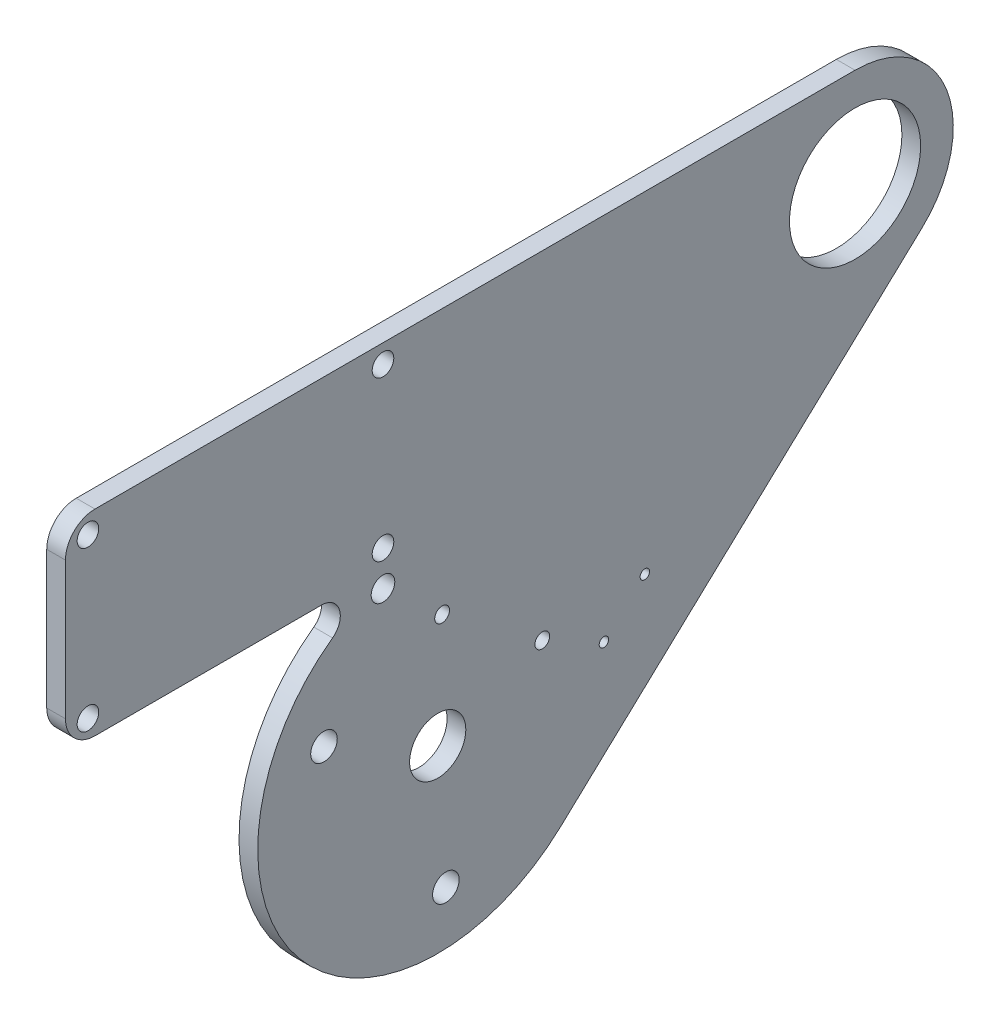
SolidWorks part; units mm, degrees
material "6061 Alloy"
ref_plane "Front Plane" through (0, 0, 0) normal (0, 0, 1) x (1, 0, 0)
ref_plane "Top Plane" through (0, 0, 0) normal (0, 1, 0) x (1, 0, 0)
ref_plane "Right Plane" through (0, 0, 0) normal (1, 0, 0) x (0, 0, -1)
sketch "Sketch1" plane through (0, 0, 0) normal (1, 0, 0) x (0, 0, -1)
  line L0 (-49.9001, -69.4268) -> (11.3662, -12.16)
  line L1 (-133.81, 16.645) -> (-76.19, 16.645)
  line L2 (-133.81, 16.645) -> (-133.81, -16.645)
  line L3 (-133.81, -16.645) -> (-76.19, -16.645)
  line L4 (-76.19, 16.645) -> (-76.19, -16.645)
  line L5 (-130, 13.475) -> (-80, 13.475)
  line L6 (-130, 13.475) -> (-130, -13.475)
  line L7 (-130, -13.475) -> (-80, -13.475)
  line L8 (-80, 13.475) -> (-80, -13.475)
  line L9 (-76.19, 16.645) -> (0, 16.645)
  line L10 (-83.2811, -19.3484) -> (-6.8511, 15.1697)
  line L11 (-130, -13.475) -> (-130, -19.435)
  line L12 (-80, -13.475) -> (-80, -19.435)
  line L13 (-76.19, -16.645) -> (0, -16.645)
  circle A0 centre (0, 0) radius 11.1125
  circle A1 centre (-70.7273, -47.145) radius 4.7625
  circle A2 centre (-70.7273, -47.145) radius 23.015 construction
  circle A3 centre (-70.7273, -47.145) radius 30.5
  circle A4 centre (0, 0) radius 16.645
  circle A5 centre (-130, -19.435) radius 2
  circle A6 centre (-80, -19.435) radius 2
  point P4 (-133.81, 0)
  point P12 (-130, 0)
  dimension "D6" = 22.225
  dimension "D7" = 9.525
  dimension "D8" = 46.03
  dimension "D9" = 61
  dimension "D11" = 0
  dimension "D14" = 4
  dimension "D1" = 33.29
  dimension "D2" = 80
  dimension "D3" = 26.95
  dimension "D4" = 50
  dimension "D5" = 3.81
  dimension "D10" = 85
  dimension "D12" = 3.81
  dimension "D13" = 5.96
extrude "Boss-Extrude1" add sketch "Sketch1" along normal mid plane 3.175 contours A6 A3 A1 | A4 L13 A3 L0 | A4 A0 | A4 L10 L4 L13 | A4 L9 L4 L10 | L8 L12 L3 L10 L4 L1 L2 L11 L6 L5 | L8 L5 L6 L7 | L12 L7 L11 L3 | A6 A3 L13 L3 L10 | L10 L3 L4 | A3 A6 | A3 A6 L10 L12 | L10 A6 A3 L12 | A6 L10 A3 region at (0, -30.4378, 28.398) region at (0, -63.5833, 95.3881) region at (0, -15.0453, -5.9367) region at (0, -18.8843, 82.226) region at (0, -7.4928, 34.7947) region at (0, -18.2558, 80.7031) region at (0, -19.6484, 79.9286) region at (0, -17.0177, 76.5839) region at (0, 5.7227, 51.9516) region at (0, -17.8085, 79.5096) region at (0, -16.4786, 76.5584) region at (0, -15.7889, 77.0165) region at (0, -15.06, 105) region at (0, 0, 105)
hole_wizard "#6 Clearance Hole1" positions "Sketch2" profile "Sketch3" hole size "#6" standard "ANSI Inch" end condition up to next
sketch "Sketch2" plane through (1.5875, 0, 0) normal (1, 0, 0) x (0, 0, -1)
  point P0 (-80, -13.475)
  point P3 (-80, 13.475)
  point P6 (-130, 13.475)
  point P9 (-130, -13.475)
sketch "Sketch3" plane through (1.5875, -13.475, 80) normal (0, 1, 0) x (0, 0, -1)
  line L0 (0, 0) -> (0, 3.175)
  line L1 (0, 3.175) -> (1.8288, 3.175)
  line L2 (1.8288, 3.175) -> (1.8288, 0)
  line L5 (1.8288, 0) -> (0, 0)
  line L11 (0, -6.35) -> (0, 107.95) construction
  dimension "Thru Hole Dia." = 3.6576
  dimension "Thru Hole Depth" = 3.175
hole_wizard "M3x0.5 Tapped Hole1" positions "Sketch4" profile "Sketch5" tap size "M3x0.5" standard "ANSI Metric" end condition up to next
sketch "Sketch4" plane through (1.5875, 0, 0) normal (1, 0, 0) x (0, 0, -1)
  line L7 (-70.7273, -47.145) -> (-41.414, -6.6391) construction
  line L9 (-69.9837, -28.2416) -> (-53.0036, -40.5297) construction
  point P121 (-61.4936, -34.3856)
  point P124 (-69.9837, -28.2416)
  point P127 (-53.0036, -40.5297)
  dimension "D1" = 20.96
  dimension "D2" = 15.75
  dimension "D3" = 135
  dimension "D4" = 50
sketch "Sketch5" plane through (1.5875, -40.5297, 53.0036) normal (0, 1, 0) x (0, 0, -1)
  line L0 (0, 0) -> (0, 3.175)
  line L1 (0, 3.175) -> (1.25, 3.175)
  line L2 (1.25, 3.175) -> (1.25, 0)
  line L5 (1.25, 0) -> (0, 0)
  line L11 (0, -6.35) -> (0, 107.95) construction
  dimension "Thru Tap Drill Dia." = 2.5
  dimension "Thru Tap Drill Depth" = 3.175
hole_wizard "M4 Clearance Hole1" positions "Sketch6" profile "Sketch7" hole size "M4" standard "ANSI Metric" end condition up to next
sketch "Sketch6" plane through (1.5875, 0, 0) normal (1, 0, 0) x (0, 0, -1)
  line L0 (-70.7273, -47.145) -> (-69.3449, -68.6005) construction
  line L1 (-70.7273, -47.145) -> (-89.9995, -37.6144) construction
  line L3 (-70.7273, -47.145) -> (0, 0) construction
  point P2 (-69.3449, -68.6005)
  point P16 (-89.9995, -37.6144)
  dimension "D1" = 21.5
  dimension "D2" = 120
  dimension "D3" = 120
sketch "Sketch7" plane through (1.5875, -37.6144, 89.9995) normal (0, 1, 0) x (0, 0, -1)
  line L0 (0, 0) -> (0, 3.175)
  line L1 (0, 3.175) -> (2.25, 3.175)
  line L2 (2.25, 3.175) -> (2.25, 0)
  line L5 (2.25, 0) -> (0, 0)
  line L11 (0, -6.35) -> (0, 107.95) construction
  dimension "Thru Hole Dia." = 4.5
  dimension "Thru Hole Depth" = 3.175
hole_wizard "M2x0.4 Tapped Hole1" positions "Sketch8" profile "Sketch9" tap size "M2x0.4" standard "ANSI Metric" end condition up to next
sketch "Sketch8" plane through (1.5875, 0, 0) normal (1, 0, 0) x (0, 0, -1)
  line L0 (-49.9001, -69.4268) -> (11.3662, -12.16) construction
  line L2 (0, 0) -> (34142.961, -36527.4995) construction
  point P0 (-35.6229, -39.5187)
  point P2 (-42.5631, -46.0059)
  dimension "D1" = 12.1
  dimension "D2" = 9.5
  dimension "D3" = 12.1
  dimension "D4" = 53.01
sketch "Sketch9" plane through (1.5875, -39.5187, 35.6229) normal (0, 1, 0) x (0, 0, -1)
  line L0 (0, 0) -> (0, 3.175)
  line L1 (0, 3.175) -> (0.8, 3.175)
  line L2 (0.8, 3.175) -> (0.8, 0)
  line L5 (0.8, 0) -> (0, 0)
  line L11 (0, -6.35) -> (0, 107.95) construction
  dimension "Thru Tap Drill Dia." = 1.6
  dimension "Thru Tap Drill Depth" = 3.175
cosmetic thread "Hole Thread1" parameters "D2"=2
cosmetic thread "Hole Thread2" parameters "D2"=2
fillet "Fillet1" radius 5 2 edges at (0, -16.645, 133.81) (0, 16.645, 133.81)
fillet "Fillet2" radius 3.175 1 edges at (0, -16.645, 77.2953)
extrude "Cut-Extrude1" cut sketch "Sketch1<3>" against normal through all both and the other way through all contours A3 A6 | A3 A6 L10 L12 | L12 A6 L10 | L10 A6 A3 L12 | L10 A6 L12 region at (0, -17.9759, 80.8435) region at (0, -18.2558, 80.7031) region at (0, -19.6484, 79.9286) region at (0, -17.6074, 79.7609) region at (0, -17.8085, 79.5096)
sketch "Sketch1<3>" plane through (0, 0, 0) normal (1, 0, 0) x (0, 0, -1) same geometry as "Sketch1"
